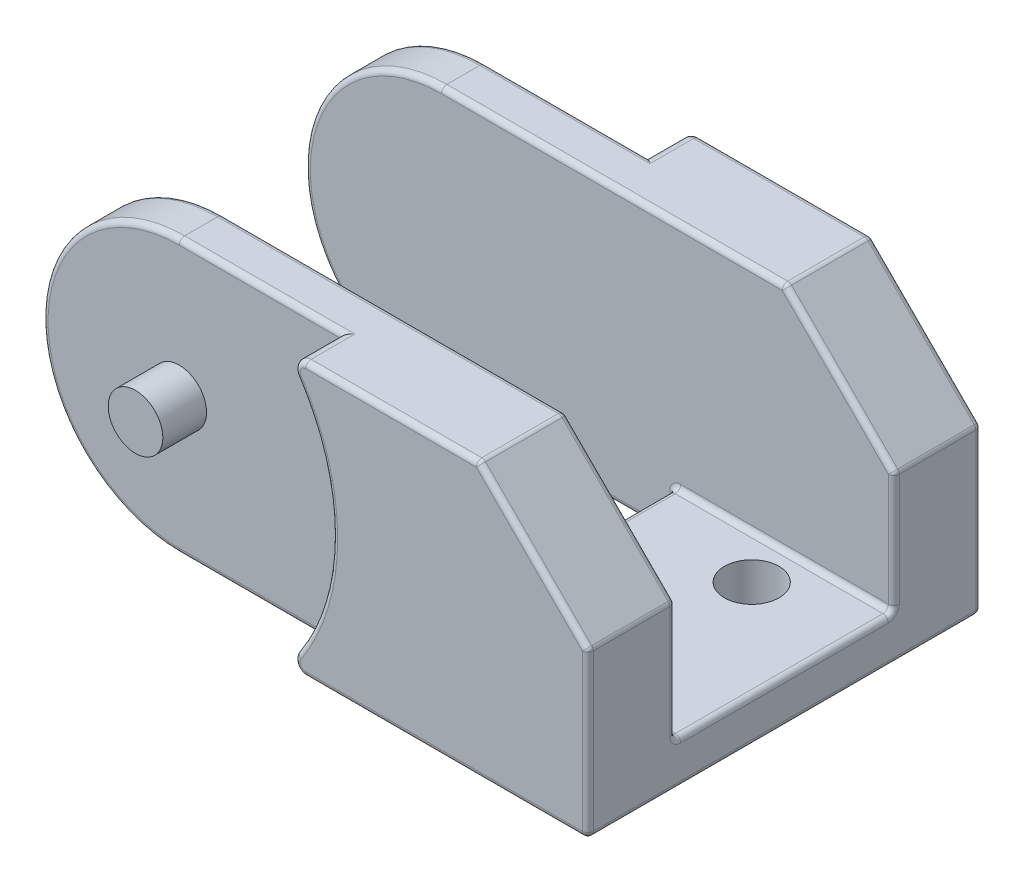
SolidWorks part; units mm, degrees
ref_plane "Front Plane" through (0, 0, 0) normal (0, 0, 1) x (1, 0, 0)
ref_plane "Top Plane" through (0, 0, 0) normal (0, 1, 0) x (1, 0, 0)
ref_plane "Right Plane" through (0, 0, 0) normal (1, 0, 0) x (0, 0, -1)
sketch "Sketch1" plane through (0, 0, 0) normal (0, 0, 1) x (1, 0, 0)
  line L0 (0, 12.5) -> (26.3875, 12.5)
  line L1 (20, 12.5) -> (20, -12.5) construction
  line L2 (26.3875, -12.5) -> (0, -12.5)
  line L3 (13.6125, -12.5) -> (40, -12.5)
  line L4 (40, 12.5) -> (13.6125, 12.5)
  circle A0 centre (0, 0) radius 12.5
  arc A1 (26.3875, -12.5) -> (26.3875, 12.5) centre (42, 0) cw
  arc A2 (13.6125, -12.5) -> (13.6125, 12.5) centre (-2, 0) ccw
  circle A3 centre (40, 0) radius 12.5
  dimension "D1" = 25
  dimension "D3" = 42
  dimension "D4" = 20
  dimension "D2" = 20
extrude "Boss-Extrude1" add sketch "Sketch1" along normal blind 4 contours A0 | L4 L1 L2 A1 | L2 A2 L0 A0 | L1 L0 A2 L3 region at (12.761, 0, 0) region at (0, 0, 0) region at (18.0615, 0, 0) region at (21.9385, 0, 0)
sketch "Sketch8" plane through (0, 0, 0) normal (0, 0, -1) x (-1, 0, 0)
  line L0 (-26.3875, 12.5) -> (-41.3875, 12.5)
  line L2 (-26.3875, -12.5) -> (-41.3875, -12.5)
  line L3 (-41.3875, -12.5) -> (-41.3875, 12.5)
  arc A0 (-26.3875, -12.5) -> (-26.3875, 12.5) centre (-42, 0) ccw construction
  arc A1 (-26.3875, -12.5) -> (-26.3875, 12.5) centre (-42, 0) ccw
  dimension "D1" = 15
extrude "Boss-Extrude7" add sketch "Sketch8" against normal blind 4
ref_plane "Plane2" through (0, 0, 14) normal (0, 0, 1) x (1, 0, 0)
mirror "Mirror3" about plane through (0, 0, 14) normal (0, 0, 1) of bodies 109
sketch "Sketch9" plane through (0, -12.5, 0) normal (0, -1, 0) x (1, 0, 0)
  line L0 (41.3875, 0) -> (0, 0) construction
  line L1 (41.3875, 28) -> (21.3875, 28)
  line L2 (41.3875, 28) -> (41.3875, 0)
  line L3 (41.3875, 0) -> (21.3875, 0)
  line L4 (21.3875, 28) -> (21.3875, 0)
  dimension "D1" = 20
extrude "Boss-Extrude8" add sketch "Sketch9" against normal blind 4
extrude "Boss-Extrude9" add sketch "Sketch1<4>" against normal blind 4 contours L1 L0 A2 L3 | L4 L1 L2 A1 | L3 A3 L4 A1 region at (18.0615, 0, 0) region at (21.9385, 0, 0) region at (27.239, 0, 0)
sketch "Sketch1<4>" plane through (0, 0, 0) normal (0, 0, 1) x (1, 0, 0) same geometry as "Sketch1"
mirror "Mirror4" about plane through (0, 0, 14) normal (0, 0, 1) of "Boss-Extrude9"
fillet "Fillet4" radius 1 4 edges at (13.6125, -12.5, 30) (13.6125, 12.5, 30) (13.6125, -12.5, -2) (13.6125, 12.5, -2)
sketch "Sketch11" plane through (0, 0, 28) normal (0, 0, 1) x (1, 0, 0)
  circle A0 centre (0, 0) radius 2.5
  dimension "D1" = 5
sketch "Sketch13" plane through (0, 0, 0) normal (0, 0, -1) x (-1, 0, 0)
  line L3 (-41.3875, -12.5) -> (-40, -12.5)
  line L4 (-40, 12.5) -> (-41.3875, 12.5)
  line L5 (-41.3875, 12.5) -> (-41.3875, -12.5)
  line L6 (-41.3875, -12.5) -> (-40, -12.5)
  line L7 (-40, 12.5) -> (-41.3875, 12.5)
  line L8 (-41.3875, 12.5) -> (-41.3875, -12.5)
  arc A1 (-40, -12.5) -> (-40, 12.5) centre (-40, 0) ccw
  arc A2 (-40, -12.5) -> (-40, 12.5) centre (-40, 0) ccw
  dimension "D1" = 0
extrude "Boss-Extrude11" add sketch "Sketch13" along normal blind 4
sketch "Sketch14" plane through (0, 0, 28) normal (0, 0, 1) x (1, 0, 0)
  line L3 (40, -12.5) -> (41.3875, -12.5)
  line L4 (41.3875, -12.5) -> (41.3875, 12.5)
  line L5 (41.3875, 12.5) -> (40, 12.5)
  line L6 (40, -12.5) -> (41.3875, -12.5)
  line L7 (41.3875, -12.5) -> (41.3875, 12.5)
  line L8 (41.3875, 12.5) -> (40, 12.5)
  arc A1 (40, 12.5) -> (40, -12.5) centre (40, 0) ccw
  arc A2 (40, 12.5) -> (40, -12.5) centre (40, 0) ccw
  dimension "D1" = 0
extrude "Boss-Extrude12" add sketch "Sketch14" along normal blind 4
sketch "Sketch15" plane through (0, -8.5, 0) normal (0, 1, 0) x (1, 0, 0)
  line L0 (41.3875, -4) -> (41.3875, -24) construction
  line L1 (41.3875, -4) -> (21.3875, -4) construction
  line L2 (41.3875, -14) -> (46.6285, -14) construction
  circle A0 centre (32.3875, -8) radius 2.5
  circle A1 centre (32.3875, -20) radius 2.5
  dimension "D1" = 5
  dimension "D2" = 9
  dimension "D3" = 4
extrude "Cut-Extrude4" cut sketch "Sketch15" against normal blind 4
chamfer "Chamfer2" distance 10 angle 45 2 edges at (41.3875, 12.5, 0) (41.3875, 12.5, 28)
extrude "Boss-Extrude13" add sketch "Sketch11" along normal blind 4 contours A0
mirror "Mirror5" about plane through (0, 0, 14) normal (0, 0, 1) of "Boss-Extrude13"
fillet "Fillet6" radius 0.5 42 edges at (21.3875, -12.5, 14) (7.7856, -12.5, 28) (-12.5, 0, 28) (7.7856, -12.5, 0) (-12.5, 0, 0) (28.4794, -12.5, -4) (14.6916, -11.9756, -4) (18, 0, -4) (14.6916, 11.9756, -4) (28.4794, -12.5, 32) (14.6916, -11.9756, 32) (14.6916, 11.9756, 32) (36.3875, 7.5, 32) (7.7856, 12.5, 28) (31.3875, 12.5, 28) (23.4794, 12.5, 32) (41.3875, -12.5, 14) (41.3875, -5, 32) (41.3875, 2.5, 28) (41.3875, -8.5, 14) (41.3875, -5, -4) (7.7856, 12.5, 0) (23.4794, 12.5, -4) (31.3875, 12.5, 0) (36.3875, 7.5, -4) (41.3875, 2.5, 0) (-12.5, 0, 24) (10.6938, -12.5, 24) (21.3875, -10.5, 24) (31.3875, -8.5, 24) (41.3875, -3, 24) (36.3875, 7.5, 24) (15.6938, 12.5, 24) (31.3875, -8.5, 4) (21.3875, -10.5, 4) (10.6938, -12.5, 4) (-12.5, 0, 4) (15.6938, 12.5, 4) (36.3875, 7.5, 4) (41.3875, -3, 4) (21.3875, -8.5, 14) (18, 0, 32)
scale "Scale1" bodies to scale 121 scale about origin uniform scaling yes scale factor 0.5
